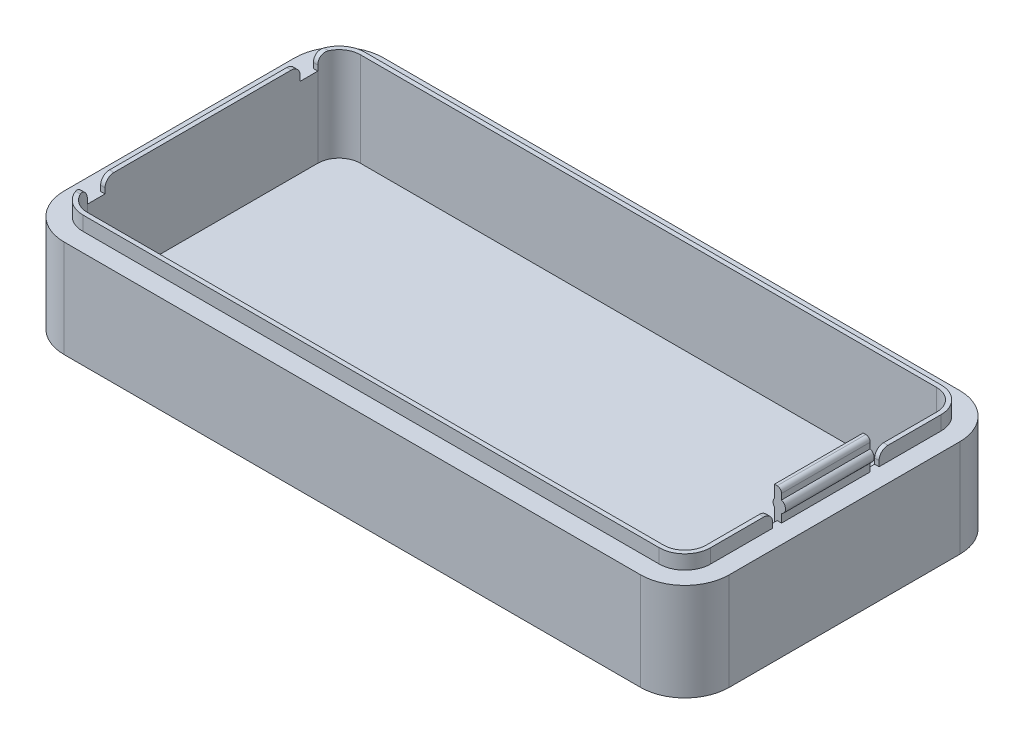
SolidWorks part; units mm, degrees
ref_plane "前视基准面" through (0, 0, 0) normal (0, 0, 1) x (1, 0, 0)
ref_plane "上视基准面" through (0, 0, 0) normal (0, 1, 0) x (1, 0, 0)
ref_plane "右视基准面" through (0, 0, 0) normal (1, 0, 0) x (0, 0, -1)
sketch "zero" plane through (0, 0, 0) normal (0, 1, 0) x (1, 0, 0)
  line L1 (-29.5, 15) -> (29.5, 15)
  line L2 (-32.5, 12) -> (-32.5, -12)
  line L3 (-29.5, -15) -> (29.5, -15)
  line L4 (32.5, 12) -> (32.5, -12)
  line L5 (-32.5, 15) -> (32.5, -15) construction
  line L6 (-32.5, -15) -> (32.5, 15) construction
  line L7 (-25.7, -15) -> (-14.5, -15)
  line L8 (-25.7, -15) -> (-25.7, -9.6569)
  line L9 (-25.7, -9.6569) -> (-14.5, -9.6569)
  line L10 (-14.5, -15) -> (-14.5, -9.6569)
  line L11 (5.2, -15) -> (12.7, -15)
  line L12 (5.2, -15) -> (5.2, -11)
  line L13 (5.2, -11) -> (12.7, -11)
  line L14 (12.7, -15) -> (12.7, -11)
  line L15 (17.8, -15) -> (25.3, -15)
  line L16 (17.8, -15) -> (17.8, -11)
  line L17 (17.8, -11) -> (25.3, -11)
  line L18 (25.3, -15) -> (25.3, -11)
  line L19 (-32.5, 7.7) -> (-19.5, 7.7)
  line L20 (-32.5, 7.7) -> (-32.5, -4.3)
  line L21 (-32.5, -4.3) -> (-19.5, -4.3)
  line L22 (-19.5, 7.7) -> (-19.5, -4.3)
  line L23 (-25.5, 14) -> (25.5, 14)
  line L24 (-25.5, 14) -> (-25.5, 8.8)
  line L25 (-25.5, 8.8) -> (25.5, 8.8)
  line L26 (25.5, 14) -> (25.5, 8.8)
  line L27 (-19.5, 7.2329) -> (-35.5, 7.2329)
  line L28 (-19.5, 7.2329) -> (-19.5, -3.7671)
  line L29 (-19.5, -3.7671) -> (-35.5, -3.7671)
  line L30 (-35.5, 7.2329) -> (-35.5, -3.7671)
  arc A0 (29.5, -15) -> (32.5, -12) centre (29.5, -12) ccw
  arc A1 (29.5, 15) -> (32.5, 12) centre (29.5, 12) cw
  arc A2 (-32.5, -12) -> (-29.5, -15) centre (-29.5, -12) ccw
  arc A3 (-29.5, 15) -> (-32.5, 12) centre (-29.5, 12) ccw
  circle A4 centre (-29, 11.4) radius 3
  circle A5 centre (-29, -11.5) radius 3
  circle A6 centre (29, 11.4) radius 3
  circle A7 centre (29, -11.5) radius 3
  circle A8 centre (-29, 11.4) radius 1.375
  circle A9 centre (-29, -11.5) radius 1.375
  circle A10 centre (29, -11.5) radius 1.375
  circle A11 centre (29, 11.4) radius 1.375
  point P0 (0, 0)
  dimension "D3" = 3
  dimension "D4" = 6
  dimension "D9" = 2.75
  dimension "D1" = 65
  dimension "D2" = 30
  dimension "D5" = 3.6
  dimension "D6" = 3.5
  dimension "D7" = 3.5
  dimension "D8" = 3.5
  dimension "D10" = 12
  dimension "D11" = 7.3
  dimension "D12" = 13
  dimension "D13" = 11.2
  dimension "D14" = 6.8
  dimension "D15" = 19.7
  dimension "D16" = 7.5
  dimension "D17" = 7.5
  dimension "D18" = 5.1
  dimension "D19" = 4
  dimension "D20" = 5.2
  dimension "D21" = 7
  dimension "D22" = 7
  dimension "D23" = 1
  dimension "D24" = 11
  dimension "D25" = 16
sketch "sugar" plane through (0, 0, 0) normal (0, 1, 0) x (1, 0, 0)
  line L1 (-29.5, 15) -> (29.5, 15)
  line L2 (-32.5, 12) -> (-32.5, -12)
  line L3 (-29.5, -15) -> (29.5, -15)
  line L4 (32.5, 12) -> (32.5, -12)
  line L5 (-32.5, 15) -> (32.5, -15) construction
  line L6 (-32.5, -15) -> (32.5, 15) construction
  line L7 (23.5, -11.5) -> (19.5, -11.5)
  line L8 (23.5, -11.5) -> (23.5, -13.9082)
  line L9 (23.5, -13.9082) -> (19.5, -13.9082)
  line L10 (19.5, -11.5) -> (19.5, -13.9082)
  line L11 (16, -11.0071) -> (8.5, -11.0071)
  line L12 (16, -11.0071) -> (16, -15)
  line L13 (16, -15) -> (8.5, -15)
  line L14 (8.5, -11.0071) -> (8.5, -15)
  line L15 (20.5, -13.9082) -> (22.5, -13.9082)
  line L16 (20.5, -13.9082) -> (20.5, -14.8173)
  line L17 (20.5, -14.8173) -> (22.5, -14.8173)
  line L18 (22.5, -13.9082) -> (22.5, -14.8173)
  arc A0 (29.5, 15) -> (32.5, 12) centre (29.5, 12) cw
  arc A1 (29.5, -15) -> (32.5, -12) centre (29.5, -12) ccw
  arc A2 (-32.5, -12) -> (-29.5, -15) centre (-29.5, -12) ccw
  arc A3 (-29.5, 15) -> (-32.5, 12) centre (-29.5, 12) ccw
  circle A4 centre (-29, 11.4) radius 3
  circle A5 centre (-29, 11.4) radius 1.375
  circle A6 centre (-29, -11.5) radius 3
  circle A7 centre (-29, -11.5) radius 1.375
  circle A8 centre (29, 11.4) radius 3
  circle A9 centre (29, 11.4) radius 1.375
  circle A10 centre (29, -11.5) radius 3
  circle A11 centre (29, -11.5) radius 1.375
  dimension "D3" = 3
  dimension "D1" = 65
  dimension "D2" = 30
  dimension "D4" = 9
  dimension "D5" = 4
  dimension "D6" = 3.5
  dimension "D7" = 7.5
  dimension "D8" = 2
  dimension "D9" = 1
sketch "case" plane through (0, 0, 0) normal (0, 1, 0) x (1, 0, 0)
  line L1 (-34.0422, 18) -> (30.9578, 18)
  line L2 (-39.0422, 13) -> (-39.0422, -13)
  line L3 (-34.0422, -18) -> (30.9578, -18)
  line L4 (35.9578, 13) -> (35.9578, -13)
  line L5 (-39.0422, 18) -> (35.9578, -18) construction
  line L6 (-39.0422, -18) -> (35.9578, 18) construction
  arc A0 (-39.0422, -13) -> (-34.0422, -18) centre (-34.0422, -13) ccw
  arc A1 (30.9578, -18) -> (35.9578, -13) centre (30.9578, -13) ccw
  arc A2 (30.9578, 18) -> (35.9578, 13) centre (30.9578, 13) cw
  arc A3 (-34.0422, 18) -> (-39.0422, 13) centre (-34.0422, 13) ccw
  point P0 (-1.5422, 0)
  point P3 (-1.5422, 0)
  dimension "D3" = 5
  dimension "D1" = 75
  dimension "D2" = 36
extrude "凸台-拉伸2" add sketch "case" along normal blind 11
sketch "草图2" plane through (0, 0, 0) normal (0, 1, 0) x (1, 0, 0)
  line L4 (-34.0422, -15.4) -> (30.9578, -15.4)
  line L5 (33.3578, -13) -> (33.3578, 13)
  line L6 (30.9578, 15.4) -> (-34.0422, 15.4)
  line L7 (-36.4422, 13) -> (-36.4422, -13)
  line L8 (33.8578, -13) -> (33.8578, 13)
  line L9 (30.9578, 15.9) -> (-34.0422, 15.9)
  line L10 (-36.9422, 13) -> (-36.9422, -13)
  line L11 (-34.0422, -15.9) -> (30.9578, -15.9)
  line L12 (33.8578, -13) -> (33.8578, 13)
  line L13 (30.9578, 15.9) -> (-34.0422, 15.9)
  line L14 (-36.9422, 13) -> (-36.9422, -13)
  line L15 (-34.0422, -15.9) -> (30.9578, -15.9)
  arc A4 (30.9578, -15.4) -> (33.3578, -13) centre (30.9578, -13) ccw
  arc A5 (33.3578, 13) -> (30.9578, 15.4) centre (30.9578, 13) ccw
  arc A6 (-34.0422, 15.4) -> (-36.4422, 13) centre (-34.0422, 13) ccw
  arc A7 (-36.4422, -13) -> (-34.0422, -15.4) centre (-34.0422, -13) ccw
  arc A8 (30.9578, -15.9) -> (33.8578, -13) centre (30.9578, -13) ccw
  arc A9 (33.8578, 13) -> (30.9578, 15.9) centre (30.9578, 13) ccw
  arc A10 (-34.0422, 15.9) -> (-36.9422, 13) centre (-34.0422, 13) ccw
  arc A11 (-36.9422, -13) -> (-34.0422, -15.9) centre (-34.0422, -13) ccw
  arc A12 (30.9578, -15.9) -> (33.8578, -13) centre (30.9578, -13) ccw
  arc A13 (33.8578, 13) -> (30.9578, 15.9) centre (30.9578, 13) ccw
  arc A14 (-34.0422, 15.9) -> (-36.9422, 13) centre (-34.0422, 13) ccw
  arc A15 (-36.9422, -13) -> (-34.0422, -15.9) centre (-34.0422, -13) ccw
  dimension "D1" = 2.1
  dimension "D2" = 0.5
ref_plane "基准面1" through (0, 11, 0) normal (0, 1, 0) x (1, 0, 0)
sketch "草图3" plane through (0, 11, 0) normal (0, 1, 0) x (1, 0, 0)
  line L4 (-34.0422, -15.4) -> (30.9578, -15.4)
  line L5 (33.3578, -13) -> (33.3578, 13)
  line L6 (30.9578, 15.4) -> (-34.0422, 15.4)
  line L7 (-36.4422, 13) -> (-36.4422, -13)
  line L8 (-34.0422, -15.4) -> (30.9578, -15.4)
  line L9 (33.3578, -13) -> (33.3578, 13)
  line L10 (30.9578, 15.4) -> (-34.0422, 15.4)
  line L11 (-36.4422, 13) -> (-36.4422, -13)
  line L12 (-36.9422, 13) -> (-36.9422, -13)
  line L13 (-34.0422, -15.9) -> (30.9578, -15.9)
  line L14 (33.8578, -13) -> (33.8578, 13)
  line L15 (30.9578, 15.9) -> (-34.0422, 15.9)
  line L16 (-36.9422, 13) -> (-36.9422, -13)
  line L17 (-34.0422, -15.9) -> (30.9578, -15.9)
  line L18 (33.8578, -13) -> (33.8578, 13)
  line L19 (30.9578, 15.9) -> (-34.0422, 15.9)
  arc A4 (30.9578, -15.4) -> (33.3578, -13) centre (30.9578, -13) ccw
  arc A5 (33.3578, 13) -> (30.9578, 15.4) centre (30.9578, 13) ccw
  arc A6 (-34.0422, 15.4) -> (-36.4422, 13) centre (-34.0422, 13) ccw
  arc A7 (-36.4422, -13) -> (-34.0422, -15.4) centre (-34.0422, -13) ccw
  arc A8 (30.9578, -15.4) -> (33.3578, -13) centre (30.9578, -13) ccw
  arc A9 (33.3578, 13) -> (30.9578, 15.4) centre (30.9578, 13) ccw
  arc A10 (-34.0422, 15.4) -> (-36.4422, 13) centre (-34.0422, 13) ccw
  arc A11 (-36.4422, -13) -> (-34.0422, -15.4) centre (-34.0422, -13) ccw
  arc A12 (-36.9422, -13) -> (-34.0422, -15.9) centre (-34.0422, -13) ccw
  arc A13 (30.9578, -15.9) -> (33.8578, -13) centre (30.9578, -13) ccw
  arc A14 (33.8578, 13) -> (30.9578, 15.9) centre (30.9578, 13) ccw
  arc A15 (-34.0422, 15.9) -> (-36.9422, 13) centre (-34.0422, 13) ccw
  arc A16 (-36.9422, -13) -> (-34.0422, -15.9) centre (-34.0422, -13) ccw
  arc A17 (30.9578, -15.9) -> (33.8578, -13) centre (30.9578, -13) ccw
  arc A18 (33.8578, 13) -> (30.9578, 15.9) centre (30.9578, 13) ccw
  arc A19 (-34.0422, 15.9) -> (-36.9422, 13) centre (-34.0422, 13) ccw
  dimension "D1" = 0
  dimension "D2" = 0
extrude "凸台-拉伸4" add sketch "草图3" along normal blind 1.6
sketch "草图5" plane through (0, 11, 0) normal (0, 1, 0) x (1, 0, 0)
  line L0 (33.3578, -13) -> (33.3578, 13) construction
  line L1 (33.0578, 5) -> (33.3578, 5)
  line L2 (33.0578, 5) -> (33.0578, -5)
  line L3 (33.0578, -5) -> (33.3578, -5)
  line L4 (33.3578, 5) -> (33.3578, -5)
  line L5 (33.0578, 5) -> (33.3578, -5) construction
  line L6 (33.0578, -5) -> (33.3578, 5) construction
  point P0 (33.2078, 0)
  dimension "D2" = 10
  dimension "D3" = 0.3
  dimension "D4" = 0
ref_plane "基准面3" through (33.8578, 0, 0) normal (1, 0, 0) x (0, 0, -1)
ref_plane "基准面7" through (-36.9422, 0, 0) normal (-1, 0, 0) x (0, 0, 1)
ref_plane "基准面8" through (0, 0, 0) normal (0, -1, 0) x (-1, 0, 0)
sketch "草图14" plane through (0, 11, 0) normal (0, 1, 0) x (1, 0, 0)
  line L4 (-34.0422, -15.4) -> (30.9578, -15.4)
  line L5 (33.3578, -13) -> (33.3578, 13)
  line L6 (30.9578, 15.4) -> (-34.0422, 15.4)
  line L7 (-36.4422, 13) -> (-36.4422, -13)
  line L8 (-34.0422, -15.4) -> (30.9578, -15.4)
  line L9 (33.3578, -13) -> (33.3578, 13)
  line L10 (30.9578, 15.4) -> (-34.0422, 15.4)
  line L11 (-36.4422, 13) -> (-36.4422, -13)
  arc A4 (30.9578, -15.4) -> (33.3578, -13) centre (30.9578, -13) ccw
  arc A5 (33.3578, 13) -> (30.9578, 15.4) centre (30.9578, 13) ccw
  arc A6 (-34.0422, 15.4) -> (-36.4422, 13) centre (-34.0422, 13) ccw
  arc A7 (-36.4422, -13) -> (-34.0422, -15.4) centre (-34.0422, -13) ccw
  arc A8 (30.9578, -15.4) -> (33.3578, -13) centre (30.9578, -13) ccw
  arc A9 (33.3578, 13) -> (30.9578, 15.4) centre (30.9578, 13) ccw
  arc A10 (-34.0422, 15.4) -> (-36.4422, 13) centre (-34.0422, 13) ccw
  arc A11 (-36.4422, -13) -> (-34.0422, -15.4) centre (-34.0422, -13) ccw
  dimension "D1" = 0
extrude "切除-拉伸2" cut sketch "草图14" against normal blind 9
extrude "凸台-拉伸12" add sketch "草图5" against normal blind 2 and the other way blind 1.6
sketch "草图17" plane through (0, 12.6, 0) normal (0, 1, 0) x (1, 0, 0)
  line L0 (33.3578, -13) -> (33.3578, -5) construction
  line L1 (33.3578, -5) -> (33.8578, -5)
  line L2 (33.3578, -5) -> (33.3578, -6)
  line L3 (33.3578, -6) -> (33.8578, -6)
  line L4 (33.8578, -5) -> (33.8578, -6)
  line L5 (33.3578, -13) -> (33.3578, 13) construction
  line L6 (33.8578, -13) -> (33.8578, 13) construction
  line L8 (33.3578, 5) -> (33.8578, 5)
  line L9 (33.3578, 5) -> (33.3578, 6)
  line L10 (33.3578, 6) -> (33.8578, 6)
  line L11 (33.8578, 5) -> (33.8578, 6)
  dimension "D1" = 1
  dimension "D2" = 1
extrude "切除-拉伸3" cut sketch "草图17" against normal blind 1.6
sketch "草图19" plane through (0, 12.6, 0) normal (0, 1, 0) x (1, 0, 0)
  line L0 (33.0578, 5) -> (33.0578, -5) construction
  line L1 (33.8578, -5) -> (33.0578, -5)
  line L2 (33.8578, -5) -> (33.8578, 5)
  line L3 (33.8578, 5) -> (33.0578, 5)
  line L4 (33.0578, -5) -> (33.0578, 5)
extrude "凸台-拉伸15" add sketch "草图19" along normal blind 1.8
sketch "草图20" plane through (0, 0, -5) normal (0, 0, -1) x (-1, 0, 0)
  line L0 (-30.9578, 11) -> (-35.9578, 11) construction
  line L3 (-33.8578, 11) -> (-33.8578, 14.4) construction
  circle A0 centre (-33.6078, 12.6) radius 0.7
  dimension "D1" = 1.4
  dimension "D2" = 1.6
  dimension "D3" = 0.25
extrude "凸台-拉伸16" add sketch "草图20" against normal blind 10
fillet "圆角4" radius 0.5 1 edges at (33.8578, 14.4, 0)
sketch "草图50" plane through (0, 12.6, 0) normal (0, 1, 0) x (1, 0, 0)
  line L0 (-36.4422, 13) -> (-36.4422, -13) construction
  line L1 (-36.4422, 13) -> (-36.9422, 13)
  line L2 (-36.4422, 13) -> (-36.4422, 11)
  line L3 (-36.4422, 11) -> (-36.9422, 11)
  line L4 (-36.9422, 13) -> (-36.9422, 11)
  line L5 (-36.9422, 13) -> (-36.9422, -13) construction
  line L6 (-36.4422, 13) -> (-36.4422, -13) construction
  line L7 (-36.4422, -11) -> (-36.9422, -11)
  line L8 (-36.4422, -11) -> (-36.4422, -13)
  line L9 (-36.4422, -13) -> (-36.9422, -13)
  line L10 (-36.9422, -11) -> (-36.9422, -13)
  line L11 (-36.9422, 13) -> (-36.9422, -13) construction
  line L12 (30.9578, 18) -> (-34.0422, 18) construction
  line L13 (-34.0422, -18) -> (30.9578, -18) construction
  dimension "D1" = 2
  dimension "D2" = 2
  dimension "D3" = 5
  dimension "D4" = 5
extrude "切除-拉伸10" cut sketch "草图50" against normal blind 1.6
fillet "圆角9" radius 1 6 edges at (33.6078, 12.6, 6) (33.6078, 12.6, -6) (-36.6922, 12.6, -13) (-36.6922, 12.6, -11) (-36.6922, 12.6, 11) (-36.6922, 12.6, 13)
sketch "草图62" plane through (0, 0, 0) normal (0, -1, 0) x (1, 0, 0)
  line L54 (31.3299, 13.3324) -> (30.9169, 13.5642)
  line L55 (30.9169, 13.5642) -> (28.7745, 14.7678)
  line L56 (28.7745, 14.7678) -> (28.3615, 15.0024)
  line L57 (27.5011, 14.9926) -> (27.0935, 14.7486)
  line L58 (27.0935, 14.7486) -> (24.9793, 13.4962)
  line L60 (24.9793, 13.4962) -> (24.5717, 13.255)
  line L61 (24.15, 12.5065) -> (24.189, 9.0989)
  line L62 (24.6278, 8.3602) -> (25.0408, 8.1284)
  line L63 (25.0408, 8.1284) -> (27.1831, 6.9248)
  line L65 (27.1831, 6.9248) -> (27.5962, 6.6902)
  line L66 (28.4566, 6.7) -> (28.8641, 6.9441)
  line L67 (28.8641, 6.9441) -> (30.9784, 8.1964)
  line L68 (30.9784, 8.1964) -> (31.3859, 8.4376)
  line L69 (31.8076, 9.1861) -> (31.7686, 12.5937)
  line L70 (25.1226, 12.9222) -> (27.7378, 14.4738)
  line L73 (28.1396, 14.4784) -> (30.7754, 12.9841)
  line L74 (30.7822, 12.6337) -> (28.2554, 11.0831)
  line L75 (29.0741, 8.5137) -> (28.7797, 8.3451)
  line L76 (28.7517, 8.2963) -> (28.7615, 7.4416)
  line L77 (28.7336, 7.3928) -> (28.1845, 7.0731)
  line L78 (28.1013, 7.1205) -> (28.0711, 9.7589)
  line L79 (28.099, 9.8076) -> (29.0331, 10.3512)
  line L80 (31.0237, 8.7127) -> (30.4803, 8.3959)
  line L81 (30.3971, 8.4434) -> (30.3827, 9.6998)
  line L82 (30.4107, 9.7486) -> (30.9541, 10.0626)
  line L83 (31.0373, 10.0151) -> (31.0517, 8.7615)
  line L84 (29.0341, 9.0205) -> (28.7735, 8.8864)
  line L85 (28.7443, 8.9459) -> (28.7366, 9.6183)
  line L86 (28.7646, 9.6671) -> (29.008, 9.8066)
  line L129 (28.7735, 8.8864) -> (28.7797, 8.3451)
  line L130 (28.7443, 8.9459) -> (28.7517, 8.2963)
  spline S0 degree 3 poles (28.3615, 15.0024) (28.2268, 15.075) (28.0782, 15.1132) (27.93, 15.1115) knots 3 3 3 3 4 4 4 4
  spline S1 degree 3 poles (27.93, 15.1115) (27.7818, 15.1098) (27.6341, 15.0682) (27.5011, 14.9926) knots 4 4 4 4 5 5 5 5
  spline S2 degree 3 poles (24.5717, 13.255) (24.3085, 13.0981) (24.1465, 12.8113) (24.15, 12.5065) knots 8 8 8 8 9 9 9 9
  spline S3 degree 3 poles (24.189, 9.0989) (24.1926, 8.7912) (24.3611, 8.511) (24.6278, 8.3602) knots 10 10 10 10 11 11 11 11
  spline S4 degree 3 poles (27.5962, 6.6902) (27.7309, 6.6148) (27.8795, 6.5794) (28.0277, 6.5811) knots 14 14 14 14 15 15 15 15
  spline S5 degree 3 poles (28.0277, 6.5811) (28.1759, 6.5828) (28.3236, 6.6216) (28.4566, 6.7) knots 15 15 15 15 16 16 16 16
  spline S6 degree 3 poles (31.3859, 8.4376) (31.652, 8.5945) (31.8112, 8.8784) (31.8076, 9.1861) knots 19 19 19 19 20 20 20 20
  spline S7 degree 3 poles (31.7686, 12.5937) (31.7651, 12.8986) (31.5995, 13.1816) (31.3299, 13.3324) knots 21 21 21 21 22 22 22 22
  spline S8 degree 2 poles (27.6998, 11.0768) (25.1072, 12.5345) (25.1014, 12.5373) knots 0 0 0 1 1 1
  spline S9 degree 3 poles (25.1014, 12.5373) (24.9664, 12.6326) (24.9783, 12.838) (25.1226, 12.9222) knots 1 1 1 1 2 2 2 2
  spline S10 degree 3 poles (27.7378, 14.4738) (27.8595, 14.5465) (28.0134, 14.5482) (28.1396, 14.4784) knots 3 3 3 3 4 4 4 4
  spline S11 degree 3 poles (30.7754, 12.9841) (30.9101, 12.9087) (30.9152, 12.715) (30.7822, 12.6337) knots 5 5 5 5 6 6 6 6
  spline S12 degree 3 poles (28.2554, 11.0831) (28.0856, 10.9815) (27.8719, 10.979) (27.6998, 11.0768) knots 7 7 7 7 8 8 8 8
  spline S13 degree 3 poles (28.7615, 7.4416) (28.7618, 7.4216) (28.7534, 7.4044) (28.7336, 7.3928) knots 3 3 3 3 4 4 4 4
  spline S14 degree 3 poles (28.1845, 7.0731) (28.1477, 7.0527) (28.1018, 7.0778) (28.1013, 7.1205) knots 5 5 5 5 6 6 6 6
  spline S15 degree 3 poles (28.0711, 9.7589) (28.0708, 9.7788) (28.0792, 9.7988) (28.099, 9.8076) knots 7 7 7 7 8 8 8 8
  spline S16 degree 3 poles (29.0331, 10.3512) (29.6389, 10.7029) (30.1424, 10.7771) (30.1502, 10.0933) knots 9 9 9 9 10 10 10 10
  spline S17 degree 3 poles (30.1502, 10.0933) (30.1577, 9.4351) (29.6544, 8.8509) (29.0741, 8.5137) knots 10 10 10 10 11 11 11 11
  spline S18 degree 3 poles (31.0517, 8.7615) (31.0519, 8.7415) (31.0407, 8.7214) (31.0237, 8.7127) knots 0 0 0 0 1 1 1 1
  spline S19 degree 3 poles (30.4803, 8.3959) (30.4435, 8.3755) (30.3976, 8.4006) (30.3971, 8.4434) knots 2 2 2 2 3 3 3 3
  spline S20 degree 3 poles (30.3827, 9.6998) (30.3825, 9.7198) (30.3937, 9.737) (30.4107, 9.7486) knots 4 4 4 4 5 5 5 5
  spline S21 degree 3 poles (30.9541, 10.0626) (30.991, 10.0829) (31.0368, 10.0578) (31.0373, 10.0151) knots 6 6 6 6 7 7 7 7
  spline S22 degree 3 poles (30.6996, 10.8946) (30.9175, 11.0224) (31.0748, 10.9701) (31.0771, 10.7707) (31.0794, 10.5741) (30.9253, 10.3415) (30.7073, 10.2165) knots 2 2 2 2 3 3 3 4 4 4 4
  spline S23 degree 3 poles (30.7073, 10.2165) (30.4866, 10.0857) (30.3293, 10.1381) (30.327, 10.3346) (30.3247, 10.5369) (30.4788, 10.7667) (30.6996, 10.8946) knots 0 0 0 0 1 1 1 2 2 2 2
  spline S24 degree 3 poles (29.5048, 9.7183) (29.5079, 9.4476) (29.3569, 9.2065) (29.0341, 9.0205) knots 0 0 0 0 1 1 1 1
  spline S25 degree 3 poles (28.7366, 9.6183) (28.7364, 9.6382) (28.7475, 9.6583) (28.7646, 9.6671) knots 4 4 4 4 5 5 5 5
  spline S26 degree 3 poles (29.008, 9.8066) (29.325, 9.9926) (29.5016, 9.9975) (29.5048, 9.7183) knots 6 6 6 6 7 7 7 7
extrude "切除-拉伸15" cut sketch "草图62" against normal blind 0.5
